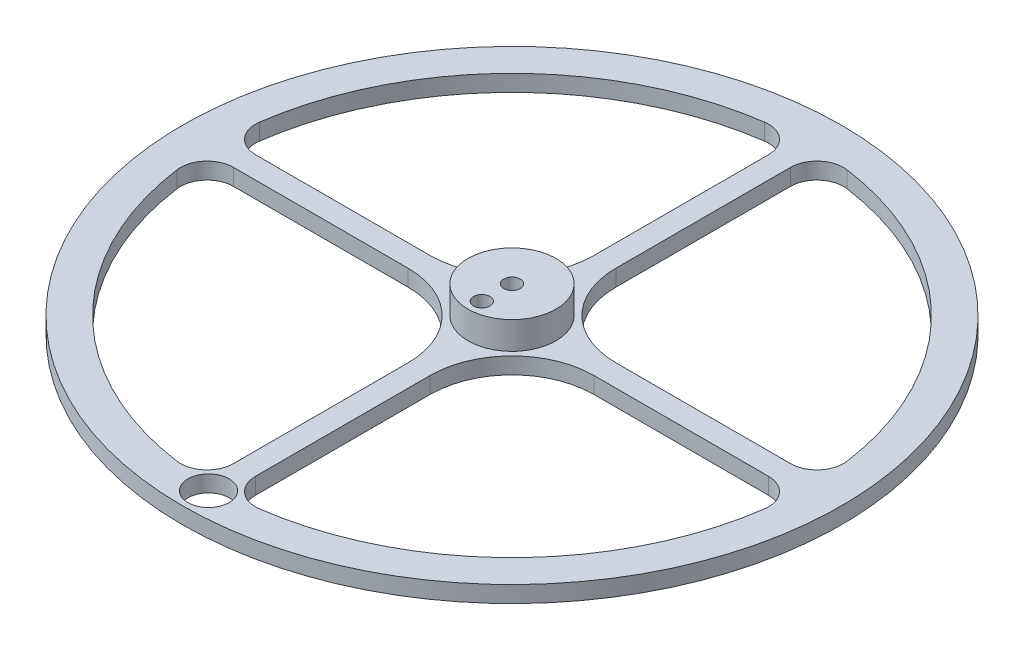
SolidWorks part; units mm, degrees
ref_plane "Front Plane" through (0, 0, 0) normal (0, 0, 1) x (1, 0, 0)
ref_plane "Top Plane" through (0, 0, 0) normal (0, 1, 0) x (1, 0, 0)
ref_plane "Right Plane" through (0, 0, 0) normal (1, 0, 0) x (0, 0, -1)
sketch "Sketch1" plane through (0, 0, 0) normal (0, 1, 0) x (1, 0, 0)
  line L0 (2, -48.6942) -> (2, -16.8995)
  line L1 (0, 0) -> (-15.5348, -15.5348) construction
  line L2 (0, 0) -> (16.1721, -16.1721) construction
  line L3 (-2, -16.8995) -> (-2, -48.6942)
  line L4 (-2, -16.8995) -> (2, -16.8995) construction
  line L5 (0, -9) -> (0, 9) construction
  line L6 (0, -60) -> (0, 9) construction
  line L7 (-16.8995, 2) -> (-48.6942, 2)
  line L8 (-48.6942, -2) -> (-16.8995, -2)
  line L9 (-11.0325, 9) -> (11.0325, 9) construction
  line L10 (0, 9) -> (0, 10.9405) construction
  line L11 (2, 16.8995) -> (2, 48.6942)
  line L12 (0, -16.8995) -> (0, -9) construction
  line L13 (-7.5, -53.4766) -> (7.5, -53.4766) construction
  line L14 (0, -60) -> (0, -53.4766) construction
  line L15 (-2, 48.6942) -> (-2, 16.8995)
  line L16 (16.8995, -2) -> (48.6942, -2)
  line L17 (48.6942, 2) -> (16.8995, 2)
  circle A0 centre (0, 0) radius 60
  circle A1 centre (0, 0) radius 54
  circle A2 centre (0, 0) radius 8
  circle A3 centre (0, 0) radius 9
  arc A4 (-16.8995, 2) -> (-6.364, 6.364) centre (-16.8995, 16.8995) ccw
  arc A5 (-2, -48.6942) -> (-7.5, -53.4766) centre (-6.8293, -48.6942) cw
  arc A6 (2, -48.6942) -> (7.5, -53.4766) centre (6.8293, -48.6942) ccw
  arc A7 (-6.364, -6.364) -> (-16.8995, -2) centre (-16.8995, -16.8995) ccw
  arc A8 (-48.6942, 2) -> (-53.4766, 7.5) centre (-48.6942, 6.8293) cw
  arc A9 (-48.6942, -2) -> (-53.4766, -7.5) centre (-48.6942, -6.8293) ccw
  arc A10 (2, 16.8995) -> (6.364, 6.364) centre (16.8995, 16.8995) ccw
  arc A11 (-6.364, 6.364) -> (-2, 16.8995) centre (-16.8995, 16.8995) ccw
  arc A12 (6.364, -6.364) -> (2, -16.8995) centre (16.8995, -16.8995) ccw
  arc A13 (-2, -16.8995) -> (-6.364, -6.364) centre (-16.8995, -16.8995) ccw
  arc A14 (2, 48.6942) -> (7.5, 53.4766) centre (6.8293, 48.6942) cw
  arc A15 (-2, 48.6942) -> (-7.5, 53.4766) centre (-6.8293, 48.6942) ccw
  arc A16 (16.8995, -2) -> (6.364, -6.364) centre (16.8995, -16.8995) ccw
  arc A18 (6.364, 6.364) -> (16.8995, 2) centre (16.8995, 16.8995) ccw
  arc A19 (48.6942, -2) -> (53.4766, -7.5) centre (48.6942, -6.8293) cw
  arc A20 (48.6942, 2) -> (53.4766, 7.5) centre (48.6942, 6.8293) ccw
  point P70 (0, 0)
  dimension "D1" = 6
  dimension "D5" = 16
  dimension "D9" = 120
  dimension "D3" = 45
  dimension "D2" = 69
  dimension "D4" = 4
  dimension "D6" = 45
  dimension "D7" = 4
  dimension "D10" = 15
extrude "Boss-Extrude1" add sketch "Sketch1" against normal blind 3 contours A0 A1 | A13 L3 A5 A1 A6 L0 A12 A7 A2 | A2 | A20 L17 A18 A3 A16 L16 A19 A1 | A3 A2 | A9 L8 A7 A3 A4 L7 A8 A1 | A15 L15 A11 A3 A10 L11 A14 A1 region at (0, 0, 31.1541) region at (0, 0, 8.7454) region at (31.1541, 0, 0) region at (-31.1541, 0, 0) region at (0, 0, -31.1541) region at (-58.3029, 0, 0) region at (0, 0, 0)
extrude "Boss-Extrude2" add sketch "Sketch1<3>" along normal blind 5 contours A2 region at (0, 0, 0)
sketch "Sketch1<3>" plane through (0, 0, 0) normal (0, 1, 0) x (1, 0, 0) same geometry as "Sketch1"
sketch "Sketch2" plane through (0, 5, 0) normal (0, 1, 0) x (1, 0, 0)
  circle A0 centre (0, 0) radius 1.5
  dimension "D1" = 3
extrude "Cut-Extrude1" cut sketch "Sketch2" against normal up to next
sketch "Sketch3" plane through (0, 0, 0) normal (0, 1, 0) x (1, 0, 0)
  line L0 (0, 0) -> (0, -55.25) construction
  circle A0 centre (0, -55.25) radius 3.75
  dimension "D1" = 7.5
  dimension "D2" = 55.25
extrude "Cut-Extrude2" cut sketch "Sketch3" against normal up to next
sketch "Sketch4" plane through (0, 5, 0) normal (0, 1, 0) x (1, 0, 0)
  line L0 (0, 0) -> (0, -5.5) construction
  circle A0 centre (0, -5.5) radius 1.5
  dimension "D2" = 3
  dimension "D1" = 5.5
extrude "Cut-Extrude3" cut sketch "Sketch4" against normal up to surface (5 mm away) up to face at (0, 0, 59)
